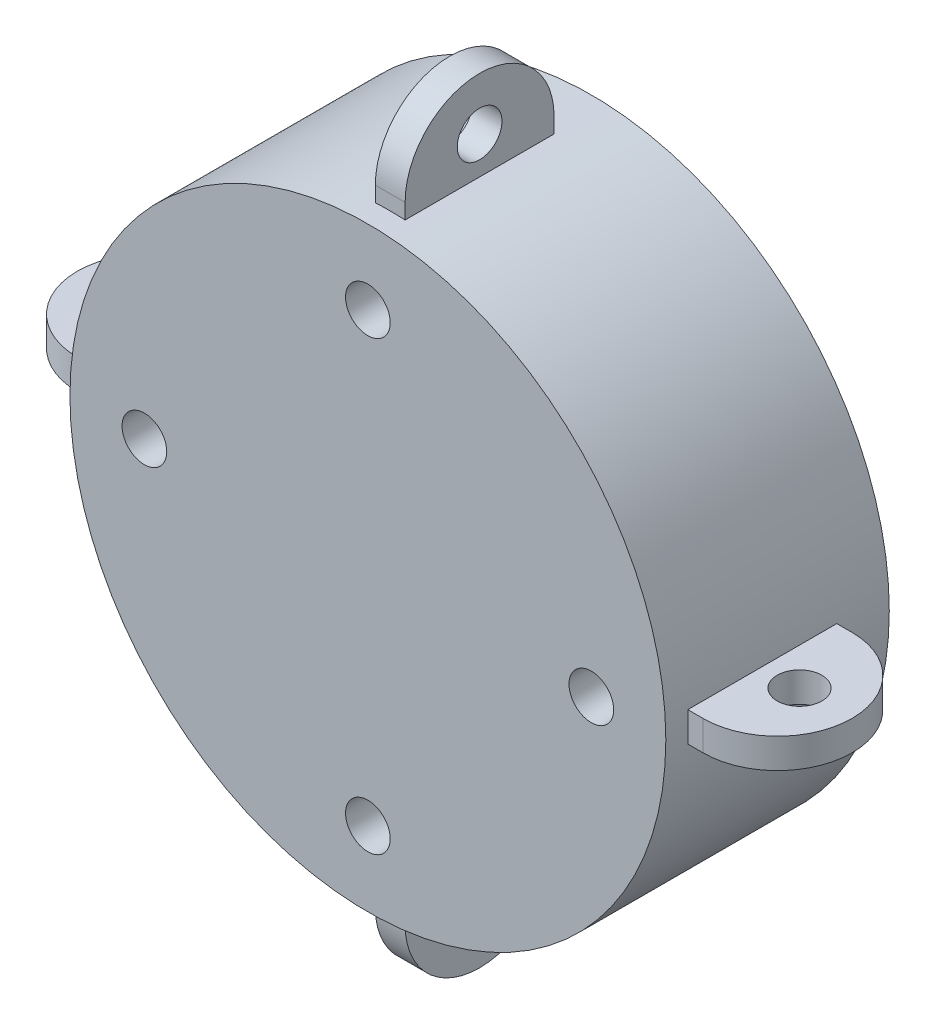
SolidWorks part; units mm, degrees
material "ABS"
ref_plane "前视基准面" through (0, 0, 0) normal (0, 0, 1) x (1, 0, 0)
ref_plane "上视基准面" through (0, 0, 0) normal (0, 1, 0) x (1, 0, 0)
ref_plane "右视基准面" through (0, 0, 0) normal (1, 0, 0) x (0, 0, -1)
sketch "草图1" plane through (0, 0, 0) normal (0, 0, 1) x (1, 0, 0)
  circle A0 centre (0, 0) radius 40
  dimension "D1" = 80
extrude "凸台-拉伸1" add sketch "草图1" along normal blind 30
sketch "草图2" plane through (0, 0, 30) normal (0, 0, 1) x (1, 0, 0)
  line L0 (0, 30) -> (0, 0) construction
  line L1 (0, 0) -> (0, -30) construction
  line L2 (-30, 0) -> (0, 0) construction
  line L3 (0, 0) -> (30, 0) construction
  circle A0 centre (30, 0) radius 3
  circle A1 centre (0, 30) radius 3
  circle A2 centre (-30, 0) radius 3
  circle A3 centre (0, -30) radius 3
  dimension "D1" = 6
  dimension "D2" = 6
  dimension "D7" = 6
  dimension "D8" = 6
  dimension "D3" = 30
  dimension "D4" = 30
  dimension "D5" = 30
  dimension "D6" = 30
extrude "切除-拉伸1" cut sketch "草图2" against normal through all
sketch "草图3" plane through (0, 0, 0) normal (1, 0, 0) x (0, 0, -1)
  line L0 (-7, 38) -> (-27, 38)
  line L1 (-27, 38) -> (-27, 42)
  line L2 (-7, 42) -> (-7, 38)
  line L3 (0, 0) -> (-35.6052, 0) construction
  arc A0 (-27, 42) -> (-7, 42) centre (-17, 42) cw
  dimension "D3" = 10
  dimension "D1" = 38
  dimension "D2" = 4
  dimension "D4" = 7
extrude "凸台-拉伸2" add sketch "草图3" along normal blind 2 and the other way blind 2
sketch "草图4" plane through (2, 0, 0) normal (1, 0, 0) x (0, 0, -1)
  line L0 (-27, 39.95) -> (-7, 39.95) construction
  line L1 (-7, 39.95) -> (-7, 42) construction
  circle A0 centre (-17, 44.95) radius 3
  dimension "D1" = 6
  dimension "D2" = 5
  dimension "D3" = 10
extrude "切除-拉伸2" cut sketch "草图4" against normal through all
pattern_circular "阵列(圆周)2" count 4 every 90 about axis through (0, 0, 30) along (0, 0, -1) of "凸台-拉伸2", "切除-拉伸2"
